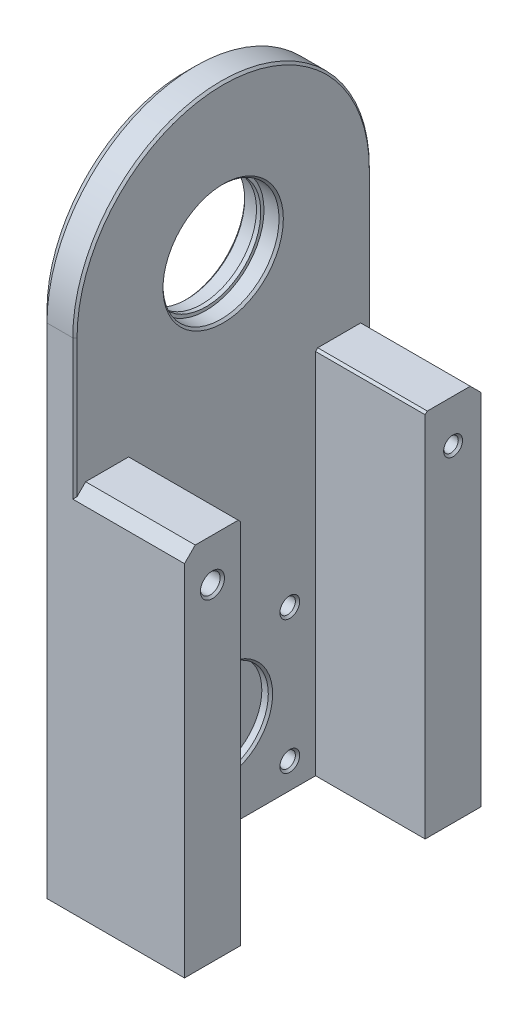
SolidWorks part; units mm, degrees
ref_plane "Ebene vorne" through (0, 0, 0) normal (0, 0, 1) x (1, 0, 0)
ref_plane "Ebene oben" through (0, 0, 0) normal (0, 1, 0) x (1, 0, 0)
ref_plane "Ebene rechts" through (0, 0, 0) normal (1, 0, 0) x (0, 0, -1)
sketch "Sketch2" plane through (0, 0, 0) normal (1, 0, 0) x (0, 0, -1)
  line L1 (0, 0) -> (69, 0)
  line L2 (0, 0) -> (0, 86)
  line L3 (0, 86) -> (69, 86)
  line L4 (69, 0) -> (69, 86)
  line L5 (0, 0) -> (69, 86) construction
  line L6 (0, 86) -> (69, 0) construction
  line L7 (0, 86) -> (69, 86)
  line L8 (0, 86) -> (0, 116)
  line L9 (0, 116) -> (69, 116)
  line L10 (69, 86) -> (69, 116)
  line L11 (0, 86) -> (69, 116) construction
  line L12 (0, 116) -> (69, 86) construction
  circle A0 centre (34.5, 116) radius 34.5
  circle A1 centre (34.5, 116) radius 12.75
  point P4 (34.5, 43)
  point P9 (34.5, 101)
  dimension "D4" = 69
  dimension "D5" = 25.5
  dimension "D1" = 69
  dimension "D2" = 86
  dimension "D3" = 30
extrude "Boss-Extrude1" add sketch "Sketch2" along normal blind 34.5 contours A0 L3 L2 L1 L4 | L7 A0 region at (0, 42.2679, -34.5) region at (0, 84.1895, -34.5)
sketch "Sketch3" plane through (34.5, 0, 0) normal (1, 0, 0) x (0, 0, -1)
  line L0 (13, 86) -> (13, 0)
  line L1 (0, 86) -> (69, 86) construction
  line L2 (0, 0) -> (69, 0) construction
  line L3 (13, 0) -> (56, 0)
  line L4 (56, 0) -> (56, 86)
  line L5 (56, 86) -> (13, 86)
  line L6 (0, 0) -> (0, 86) construction
  line L7 (69, 0) -> (69, 86) construction
  line L9 (13, 0) -> (56, 0)
  line L10 (13, 0) -> (13, 43)
  line L11 (13, 43) -> (56, 43)
  line L12 (56, 0) -> (56, 43)
  line L13 (13, 0) -> (56, 43) construction
  line L14 (13, 43) -> (56, 0) construction
  line L15 (56, 43) -> (13, 43)
  line L16 (56, 43) -> (56, 86)
  line L17 (56, 86) -> (13, 86)
  line L18 (13, 43) -> (13, 86)
  line L19 (56, 43) -> (13, 86) construction
  line L20 (56, 86) -> (13, 43) construction
  circle A0 centre (34.5, 21.5) radius 11
  circle A1 centre (34.5, 21.5) radius 5
  point P15 (34.5, 21.5)
  point P19 (34.5, 64.5)
  line M14 (69, 86) -> (0, 86)
  line M16 (0, 0) -> (69, 0)
  dimension "D3" = 22
  dimension "D4" = 10
  dimension "D1" = 13
  dimension "D2" = 13
extrude "Cut-Extrude1" cut sketch "Sketch3" against normal offset from surface (25.5 mm away) 9 contours L0 L11 L4 M14 | A0 A1 | A1 | L11 L0 L4 A0 M16 region at (34.5, 64.5, -34.5) region at (34.5, 42.3919, -34.5) region at (34.5, 21.5, -23.8111) region at (34.5, 21.5, -34.5) up to face at (0, 43, -34.5)
extrude "Boss-Extrude2" add sketch "Sketch2<3>" along normal up to surface (9 mm away) contours L9 A0 L7 | A0 L3 L10 | A0 L8 L3 | L9 A0 region at (0, 93.069, -4.894) region at (0, 93.069, -64.106) region at (0, 100.9752, -34.5) region at (0, 132.1024, -34.5) up to face at (9, 43, -34.5)
sketch "Sketch2<3>" plane through (0, 0, 0) normal (1, 0, 0) x (0, 0, -1) same geometry as "Sketch2"
extrude "Cut-Extrude2" cut sketch "Sketch3<3>" against normal offset from surface (27.5 mm away) 2 contours A0 A1 | A1 region at (34.5, 21.5, -23.8111) region at (34.5, 21.5, -34.5) up to face at (9, 76.3125, -34.5) offset beyond the face yes
sketch "Sketch3<3>" plane through (34.5, 0, 0) normal (1, 0, 0) x (0, 0, -1) same geometry as "Sketch3"
extrude "Cut-Extrude3" cut sketch "Sketch3<4>" against normal through all contours A1 region at (34.5, 21.5, -34.5)
sketch "Sketch3<4>" plane through (34.5, 0, 0) normal (1, 0, 0) x (0, 0, -1) same geometry as "Sketch3"
sketch "Sketch15" plane through (9, 0, 0) normal (1, 0, 0) x (0, 0, -1)
  circle A0 centre (34.5, 116) radius 13.5
  dimension "D1" = 27
extrude "Cut-Extrude4" cut sketch "Sketch15" against normal blind 4
ref_plane "Plane1" through (4.5, 0, 0) normal (1, 0, 0) x (0, 0, -1)
mirror "Mirror1" about plane through (4.5, 0, 0) normal (1, 0, 0) of "Cut-Extrude4"
hole_wizard "CBORE for M3 Hex Socket Head Cap Screw1" positions "Sketch4" profile "Sketch5" counterbore size "M3" standard "DIN" end condition through all
sketch "Sketch4" plane through (0, 0, 0) normal (-1, 0, 0) x (0, 0, 1)
  line L1 (-50, 6) -> (-19, 6)
  line L2 (-50, 6) -> (-50, 37)
  line L3 (-50, 37) -> (-19, 37)
  line L4 (-19, 6) -> (-19, 37)
  line L5 (-50, 6) -> (-19, 37) construction
  line L6 (-50, 37) -> (-19, 6) construction
  point P0 (-34.5, 21.5)
  point P1 (-19, 37)
  point P4 (-50, 6)
  point P5 (-50, 37)
  point P6 (-19, 6)
  dimension "D1" = 31
sketch "Sketch5" plane through (0, 6, -19) normal (0, 1, 0) x (0, 0, 1)
  line L0 (0, 0) -> (0, 34.5)
  line L1 (0, 34.5) -> (1.8, 34.5)
  line L3 (1.8, 34.5) -> (1.8, 3.4)
  line L4 (1.8, 3.4) -> (3.25, 3.4)
  line L5 (3.25, 3.4) -> (3.25, 0)
  line L7 (3.25, 0) -> (0, 0)
  line L11 (0, -6.35) -> (0, 107.95) construction
  dimension "Thru Hole Dia." = 3.6
  dimension "Thru Hole Depth" = 34.5
  dimension "C'Bore Dia." = 6.5
  dimension "C'Bore Depth" = 3.4
hole_wizard "Ø4.6 (4.6) Diameter Hole1" positions "Sketch8" profile "Sketch9" hole size "Ø4.6" standard "DIN"
sketch "Sketch8" plane through (0, 0, 0) normal (0, -1, 0) x (-1, 0, 0)
  line L0 (-34.5, 69) -> (-34.5, 0) construction
  line L1 (-34.5, 0) -> (0, 0) construction
  line L2 (-34.5, 0) -> (-34.5, 13) construction
  line L5 (-64.5, 6.5) -> (-4.5, 6.5)
  line L6 (-64.5, 6.5) -> (-64.5, 62.5)
  line L7 (-64.5, 62.5) -> (-4.5, 62.5)
  line L8 (-4.5, 6.5) -> (-4.5, 62.5)
  line L9 (-64.5, 6.5) -> (-4.5, 62.5) construction
  line L10 (-64.5, 62.5) -> (-4.5, 6.5) construction
  line L11 (-34.5, 69) -> (0, 69) construction
  line L12 (0, 0) -> (0, 69) construction
  point P9 (-34.5, 34.5)
  point P10 (-4.5, 62.5)
  point P15 (-4.5, 6.5)
  point P89 (-4.5, 34.5)
  dimension "D1" = 6.5
  dimension "D2" = 4.5
sketch "Sketch9" plane through (4.5, 0, -34.5) normal (1, 0, 0) x (0, 0, -1)
  line L0 (0, 0) -> (0, 7.382)
  line L1 (0, 7.382) -> (2.3, 6)
  line L2 (2.3, 6) -> (2.3, 0)
  line L5 (2.3, 0) -> (0, 0)
  line L10 (0, 7.382) -> (-2.3, 6) construction
  line L11 (0, -6.35) -> (0, 107.95) construction
  dimension "Hole Dia." = 4.6
  dimension "Hole Depth" = 6
  dimension "Drill Angle" = 118
hole_wizard "CBORE for M3 Hex Socket Head Cap Screw2" positions "Sketch10" profile "Sketch11" counterbore size "M3" standard "DIN" end condition through all
sketch "Sketch10" plane through (0, 0, 0) normal (-1, 0, 0) x (0, 0, 1)
  line L0 (-56, 86) -> (-69, 86) construction
  line L1 (-56, 86) -> (-69, 86)
  line L2 (-62.5, 86) -> (-62.5, 76) construction
  point P4 (-62.5, 76)
  dimension "D1" = 10
sketch "Sketch11" plane through (0, 76, -62.5) normal (0, 1, 0) x (0, 0, 1)
  line L0 (0, 0) -> (0, 34.5)
  line L1 (0, 34.5) -> (1.7, 34.5)
  line L3 (1.7, 34.5) -> (1.7, 3.4)
  line L4 (1.7, 3.4) -> (3.25, 3.4)
  line L5 (3.25, 3.4) -> (3.25, 0)
  line L7 (3.25, 0) -> (0, 0)
  line L11 (0, -6.35) -> (0, 107.95) construction
  dimension "Thru Hole Dia." = 3.4
  dimension "Thru Hole Depth" = 34.5
  dimension "C'Bore Dia." = 6.5
  dimension "C'Bore Depth" = 3.4
hole_wizard "Ø4.6 (4.6) Diameter Hole2" positions "Sketch12" profile "Sketch14" hole size "Ø4.6" standard "DIN"
sketch "Sketch12" plane through (34.5, 0, 0) normal (1, 0, 0) x (0, 0, -1)
  line L0 (6.5, 86) -> (6.5, 76) construction
  line L1 (0, 86) -> (13, 86) construction
  point P1 (6.5, 76)
  dimension "D1" = 10
sketch "Sketch14" plane through (34.5, 76, -6.5) normal (0, 1, 0) x (0, 0, -1)
  line L0 (0, 0) -> (0, 7.382)
  line L1 (0, 7.382) -> (2.3, 6)
  line L2 (2.3, 6) -> (2.3, 0)
  line L5 (2.3, 0) -> (0, 0)
  line L10 (0, 7.382) -> (-2.3, 6) construction
  line L11 (0, -6.35) -> (0, 107.95) construction
  dimension "Hole Dia." = 4.6
  dimension "Hole Depth" = 6
  dimension "Drill Angle" = 118
hole_wizard "Ø4.6 (4.6) Diameter Hole3" positions "Sketch18" profile "Sketch17" hole size "Ø4.6" standard "DIN"
sketch "Sketch18" plane through (0, 0, 0) normal (-1, 0, 0) x (0, 0, 1)
  line L0 (-34.5, 21.5) -> (-34.5, 116) construction
  point P9 (-9.5, 68.75)
  point P18 (-34.5, 68.75)
  point P20 (-59.5, 68.75)
  dimension "D1" = 25
sketch "Sketch17" plane through (0, 68.75, -59.5) normal (0, 1, 0) x (0, 0, 1)
  line L0 (0, 0) -> (0, 6.382)
  line L1 (0, 6.382) -> (2.3, 5)
  line L2 (2.3, 5) -> (2.3, 0)
  line L5 (2.3, 0) -> (0, 0)
  line L10 (0, 6.382) -> (-2.3, 5) construction
  line L11 (0, -6.35) -> (0, 107.95) construction
  dimension "Hole Dia." = 4.6
  dimension "Hole Depth" = 5
  dimension "Drill Angle" = 118
chamfer "2,5mm Chamfer1" distance 2.5 angle 45 5 edges at (21.75, 86, -69) (21.75, 86, 0) (0, 58, 0) (0, 150.5, -34.5) (0, 58, -69)
chamfer "0,5mm Chamfer2" distance 0.5 angle 45 26 edges at (0, 21.5, -39.5) (7, 21.5, -39.5) (9, 21.5, -45.5) (4.5, 0, -8.8) (4.5, 0, -36.8) (4.5, 0, -64.8) (9, 6, -20.8) (9, 6, -51.8) (9, 37, -51.8) (9, 37, -20.8) (34.5, 76, -60.8) (34.5, 76, -8.8) (9, 99.75, -69) (9, 99.75, 0) (9, 150.5, -34.5) (0, 6, -15.75) (0, 6, -46.75) (0, 37, -15.75) (0, 37, -46.75) (0, 76, -59.25) (21.75, 86, -56) (21.75, 86, -13) (0, 116, -48) (9, 116, -48) (0, 68.75, -7.2) (0, 68.75, -57.2)
